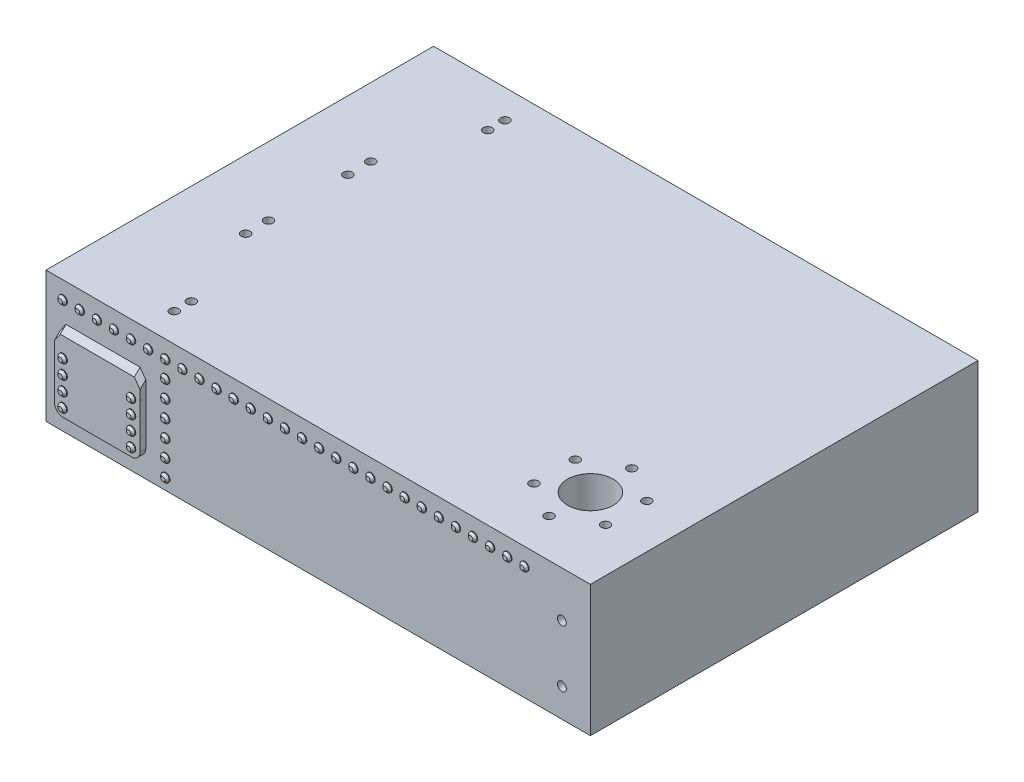
SolidWorks part; units mm, degrees
ref_plane "Front Plane" through (0, 0, 0) normal (0, 0, 1) x (1, 0, 0)
ref_plane "Top Plane" through (0, 0, 0) normal (0, 1, 0) x (1, 0, 0)
ref_plane "Right Plane" through (0, 0, 0) normal (1, 0, 0) x (0, 0, -1)
sketch "Sketch1" plane through (0, 0, 0) normal (0, 1, 0) x (1, 0, 0)
  line L1 (0, 0) -> (191, 0)
  line L2 (0, 0) -> (0, 136)
  line L3 (0, 136) -> (191, 136)
  line L4 (191, 0) -> (191, 136)
  dimension "D1" = 191
  dimension "D2" = 136
extrude "Boss-Extrude1" add sketch "Sketch1" along normal blind 46
sketch "Sketch3" plane through (0, 0, 0) normal (0, -1, 0) x (1, 0, 0)
  line L0 (0, -136) -> (0, 0) construction
  line L1 (5, -5) -> (186, -5)
  line L2 (5, -5) -> (5, -131)
  line L3 (5, -131) -> (186, -131)
  line L4 (186, -5) -> (186, -131)
  line L6 (191, -136) -> (0, -136) construction
  line L7 (191, 0) -> (191, -136) construction
  line L8 (0, 0) -> (191, 0) construction
  dimension "D1" = 5
  dimension "D2" = 5
  dimension "D3" = 5
  dimension "D4" = 5
extrude "Cut-Extrude1" cut sketch "Sketch3" against normal offset from surface (41 mm away) 5 contours L2 L3 L4 L1 up to face at (95.5, 46, -68)
ref_point "FrontLeft"
sketch "Sketch5" plane through (0, 0, -136) normal (0, 0, -1) x (-1, 0, 0)
  line L0 (-191, 46) -> (-119.5, 46)
  line L1 (-191, 46) -> (0, 46) construction
  line L2 (-119.5, 46) -> (-119.5, 0) construction
  line L3 (-191, 0) -> (0, 0) construction
  point P5 (-119.5, 23)
  dimension "D1" = 71.5
sketch "Sketch8" plane through (0, 0, 0) normal (0, 0, 1) x (1, 0, 0)
  line L1 (119.5, 46) -> (119.5, 0) construction
  line L2 (0, 46) -> (191, 46) construction
  line L3 (0, 0) -> (191, 0) construction
  point P0 (119.5, 23)
ref_point "SuspensionMountLeft"
ref_point "SuspensionMountRight"
sketch "Sketch9" plane through (0, 0, -136) normal (0, 0, -1) x (-1, 0, 0)
  line L0 (0, 46) -> (0, 0) construction
  line L1 (-5, 31) -> (-35, 31)
  line L2 (-5, 31) -> (-5, 6.2153)
  line L3 (-5, 6.2153) -> (-35, 6.2153)
  line L4 (-35, 31) -> (-35, 6.2153)
  line L5 (-191, 46) -> (0, 46) construction
  dimension "D1" = 5
  dimension "D2" = 15
  dimension "D3" = 30
extrude "Boss-Extrude2" add sketch "Sketch9" along normal blind 2
chamfer "Chamfer2" distance 2 angle 45 1 edges at (20, 31, -136)
fillet "Fillet1" radius 3 2 edges at (35, 6.2153, -137) (5, 6.2153, -137)
chamfer "Chamfer3" distance 2 angle 45 2 edges at (35, 32, -137) (5, 32, -137)
sketch "Sketch10" plane through (0, 0, 0) normal (0, 0, 1) x (1, 0, 0)
  line L4 (35, 31) -> (5, 31)
  line L5 (35, 6.2153) -> (35, 31)
  line L6 (5, 6.2153) -> (35, 6.2153)
  line L7 (5, 31) -> (5, 6.2153)
  line L8 (35, 31) -> (5, 31)
  line L9 (35, 6.2153) -> (35, 31)
  line L10 (5, 6.2153) -> (35, 6.2153)
  line L11 (5, 31) -> (5, 6.2153)
  dimension "D1" = 0
extrude "Boss-Extrude3" add sketch "Sketch10" along normal blind 2
chamfer "Chamfer4" distance 2 angle 45 1 edges at (20, 31, 0)
fillet "Fillet2" radius 3 2 edges at (35, 6.2153, 1) (5, 6.2153, 1)
chamfer "Chamfer5" distance 2 angle 45 2 edges at (35, 32, 1) (5, 32, 1)
sketch "Sketch23" plane through (0, 0, 2) normal (0, 0, 1) x (1, 0, 0)
  line L0 (8, 9.2153) -> (8, 31) construction
  line L1 (33, 31) -> (7, 31) construction
  line L2 (32, 9.2153) -> (32, 31) construction
  circle A0 centre (8, 9.2153) radius 1.5
  circle A1 centre (32, 9.2153) radius 1.5
  circle A2 centre (8, 14.2153) radius 1.5
  circle A3 centre (32, 14.2153) radius 1.5
  circle A4 centre (8, 19.2153) radius 1.5
  circle A5 centre (32, 19.2153) radius 1.5
  circle A6 centre (8, 24.2153) radius 1.5
  circle A7 centre (32, 24.2153) radius 1.5
  dimension "D1" = 3
  dimension "D2" = 3
  dimension "D3" = 4
extrude "Boss-Extrude8" add sketch "Sketch23" along normal blind 1 contours A4 | A2 | A0 | A1 | A3 | A5 | A7 | A6 region at (8, 9.2153, 2) region at (32, 9.2153, 2) region at (8, 14.2153, 2) region at (32, 14.2153, 2) region at (8, 19.2153, 2) region at (32, 19.2153, 2) region at (32, 24.2153, 2)
chamfer "Chamfer11" distance 0.75 angle 45 8 edges at (9.5, 24.2153, 3) (33.5, 9.2153, 3) (33.5, 14.2153, 3) (33.5, 19.2153, 3) (33.5, 24.2153, 3) (9.5, 9.2153, 3) (9.5, 14.2153, 3) (9.5, 19.2153, 3)
ref_plane "Plane1" through (0, 0, -68) normal (0, 0, 1) x (1, 0, 0)
mirror "Mirror1" about plane through (0, 0, -68) normal (0, 0, 1) of "Chamfer11", "Boss-Extrude8"
sketch "Sketch18" plane through (0, 41, 0) normal (0, -1, 0) x (1, 0, 0)
  line L1 (112.6585, -114) -> (114.6793, -117.5)
  line L2 (114.6793, -117.5) -> (118.7207, -117.5)
  line L3 (118.7207, -117.5) -> (120.7415, -114)
  line L4 (120.7415, -114) -> (118.7207, -110.5)
  line L5 (118.7207, -110.5) -> (114.6793, -110.5)
  line L6 (114.6793, -110.5) -> (112.6585, -114)
  line L7 (112.6585, -66) -> (114.6793, -69.5)
  line L8 (114.6793, -69.5) -> (118.7207, -69.5)
  line L9 (118.7207, -69.5) -> (120.7415, -66)
  line L10 (120.7415, -66) -> (118.7207, -62.5)
  line L11 (118.7207, -62.5) -> (114.6793, -62.5)
  line L12 (114.6793, -62.5) -> (112.6585, -66)
  line L13 (12.4585, -67) -> (14.4793, -70.5)
  line L14 (14.4793, -70.5) -> (18.5207, -70.5)
  line L15 (18.5207, -70.5) -> (20.5415, -67)
  line L16 (20.5415, -67) -> (18.5207, -63.5)
  line L17 (18.5207, -63.5) -> (14.4793, -63.5)
  line L18 (14.4793, -63.5) -> (12.4585, -67)
  line L19 (12.4585, -119.5) -> (14.4793, -123)
  line L20 (14.4793, -123) -> (18.5207, -123)
  line L21 (18.5207, -123) -> (20.5415, -119.5)
  line L22 (20.5415, -119.5) -> (18.5207, -116)
  line L23 (18.5207, -116) -> (14.4793, -116)
  line L24 (14.4793, -116) -> (12.4585, -119.5)
  circle A0 centre (116.7, -114) radius 3.5 construction
  circle A9 centre (116.7, -66) radius 3.5 construction
  circle A10 centre (16.5, -67) radius 3.5 construction
  circle A11 centre (16.5, -119.5) radius 3.5 construction
  point P41 (116.7, -114)
  point P42 (116.7, -66)
  point P43 (16.5, -67)
  point P44 (16.5, -119.5)
extrude "Boss-Extrude7" add sketch "Sketch18" along normal blind 14
sketch "Sketch19" plane through (0, 27, 0) normal (0, -1, 0) x (1, 0, 0)
  line L6 (112.6585, -66) -> (114.6793, -69.5)
  line L7 (114.6793, -69.5) -> (118.7207, -69.5)
  line L8 (118.7207, -69.5) -> (120.7415, -66)
  line L9 (120.7415, -66) -> (118.7207, -62.5)
  line L10 (118.7207, -62.5) -> (114.6793, -62.5)
  line L11 (114.6793, -62.5) -> (112.6585, -66)
  line L12 (112.6585, -66) -> (114.6793, -69.5)
  line L13 (114.6793, -69.5) -> (118.7207, -69.5)
  line L14 (118.7207, -69.5) -> (120.7415, -66)
  line L15 (120.7415, -66) -> (118.7207, -62.5)
  line L16 (118.7207, -62.5) -> (114.6793, -62.5)
  line L17 (114.6793, -62.5) -> (112.6585, -66)
  line L18 (120.7415, -114) -> (118.7207, -110.5)
  line L19 (118.7207, -110.5) -> (114.6793, -110.5)
  line L20 (114.6793, -110.5) -> (112.6585, -114)
  line L21 (112.6585, -114) -> (114.6793, -117.5)
  line L22 (114.6793, -117.5) -> (118.7207, -117.5)
  line L23 (118.7207, -117.5) -> (120.7415, -114)
  line L24 (120.7415, -114) -> (118.7207, -110.5)
  line L25 (118.7207, -110.5) -> (114.6793, -110.5)
  line L26 (114.6793, -110.5) -> (112.6585, -114)
  line L27 (112.6585, -114) -> (114.6793, -117.5)
  line L28 (114.6793, -117.5) -> (118.7207, -117.5)
  line L29 (118.7207, -117.5) -> (120.7415, -114)
  line L30 (12.4585, -119.5) -> (14.4793, -123)
  line L31 (14.4793, -123) -> (18.5207, -123)
  line L32 (18.5207, -123) -> (20.5415, -119.5)
  line L33 (20.5415, -119.5) -> (18.5207, -116)
  line L34 (18.5207, -116) -> (14.4793, -116)
  line L35 (14.4793, -116) -> (12.4585, -119.5)
  line L36 (12.4585, -119.5) -> (14.4793, -123)
  line L37 (14.4793, -123) -> (18.5207, -123)
  line L38 (18.5207, -123) -> (20.5415, -119.5)
  line L39 (20.5415, -119.5) -> (18.5207, -116)
  line L40 (18.5207, -116) -> (14.4793, -116)
  line L41 (14.4793, -116) -> (12.4585, -119.5)
  line L42 (18.5207, -63.5) -> (14.4793, -63.5)
  line L43 (20.5415, -67) -> (18.5207, -63.5)
  line L44 (18.5207, -70.5) -> (20.5415, -67)
  line L45 (14.4793, -70.5) -> (18.5207, -70.5)
  line L46 (12.4585, -67) -> (14.4793, -70.5)
  line L47 (14.4793, -63.5) -> (12.4585, -67)
  line L48 (18.5207, -63.5) -> (14.4793, -63.5)
  line L49 (20.5415, -67) -> (18.5207, -63.5)
  line L50 (18.5207, -70.5) -> (20.5415, -67)
  line L51 (14.4793, -70.5) -> (18.5207, -70.5)
  line L52 (12.4585, -67) -> (14.4793, -70.5)
  line L53 (14.4793, -63.5) -> (12.4585, -67)
  circle A0 centre (116.7, -66) radius 4.0415
  circle A1 centre (16.5, -67) radius 4.0415
  circle A2 centre (16.5, -119.5) radius 4.0415
  circle A3 centre (116.7, -114) radius 4.0415
  dimension "D1" = 0
  dimension "D2" = 0
  dimension "D3" = 0
  dimension "D4" = 0
hole_wizard "CSK for M2 Flat Head Machine Screw1" positions "Sketch21" profile "Sketch20" countersink size "M2" standard "ANSI Metric"
sketch "Sketch21" plane through (0, 27, 0) normal (0, -1, 0) x (-1, 0, 0)
  point P0 (-116.7, 114)
  point P3 (-116.7, 66)
  point P6 (-16.5, 67)
  point P9 (-16.5, 119.5)
sketch "Sketch20" plane through (116.7, 27, -114) normal (1, 0, 0) x (0, 0, -1)
  line L0 (0, 0) -> (0, 13.6009)
  line L1 (0, 13.6009) -> (1, 13)
  line L2 (1, 13) -> (1, 0.4195)
  line L3 (1, 0.4195) -> (1.5, 0)
  line L5 (1.5, 0) -> (0, 0)
  line L6 (-1, 0.4195) -> (-1.5, 0) construction
  line L10 (0, 13.6009) -> (-1, 13) construction
  line L11 (0, -6.35) -> (0, 107.95) construction
  dimension "Hole Dia." = 2
  dimension "Hole Depth" = 13
  dimension "Near C'Sink Dia." = 3
  dimension "Near C'Sink Angle" = 100
  dimension "Drill Angle" = 118
sketch "Sketch22" plane through (0, 0, 0) normal (-1, 0, 0) x (0, 0, 1)
  line L0 (0, 46) -> (0, 0) construction
  line L1 (-10, 10) -> (-80, 10)
  line L2 (-10, 10) -> (-10, 38)
  line L3 (-10, 38) -> (-80, 38)
  line L4 (-80, 10) -> (-80, 38)
  line L5 (-136, 0) -> (0, 0) construction
  line L6 (-136, 46) -> (0, 46) construction
  dimension "D1" = 10
  dimension "D2" = 10
  dimension "D3" = 8
  dimension "D4" = 70
extrude "Cut-Extrude2" [suppressed] cut sketch "Sketch22" against normal up to next
chamfer "Chamfer10" [suppressed] distance 28 angle 45
fillet "Fillet3" [suppressed] radius 3
sketch "Sketch24" plane through (0, 0, 0) normal (0, 0, 1) x (1, 0, 0)
  line L0 (0, 40) -> (191, 40) construction
  line L1 (0, 46) -> (0, 0) construction
  line L2 (191, 46) -> (191, 0) construction
  line L3 (0, 46) -> (191, 46) construction
  circle A0 centre (6, 40) radius 1.5
  circle A1 centre (12, 40) radius 1.5
  circle A2 centre (18, 40) radius 1.5
  circle A3 centre (24, 40) radius 1.5
  circle A4 centre (30, 40) radius 1.5
  circle A5 centre (36, 40) radius 1.5
  circle A6 centre (42, 40) radius 1.5
  circle A7 centre (48, 40) radius 1.5
  circle A8 centre (54, 40) radius 1.5
  circle A9 centre (60, 40) radius 1.5
  circle A10 centre (66, 40) radius 1.5
  circle A11 centre (72, 40) radius 1.5
  circle A12 centre (78, 40) radius 1.5
  circle A13 centre (84, 40) radius 1.5
  circle A14 centre (90, 40) radius 1.5
  circle A15 centre (96, 40) radius 1.5
  circle A16 centre (102, 40) radius 1.5
  circle A17 centre (108, 40) radius 1.5
  circle A18 centre (114, 40) radius 1.5
  circle A19 centre (120, 40) radius 1.5
  circle A20 centre (126, 40) radius 1.5
  circle A21 centre (132, 40) radius 1.5
  circle A22 centre (138, 40) radius 1.5
  circle A23 centre (144, 40) radius 1.5
  circle A24 centre (150, 40) radius 1.5
  circle A25 centre (156, 40) radius 1.5
  circle A26 centre (162, 40) radius 1.5
  circle A27 centre (168, 40) radius 1.5
  circle A28 centre (42, 34) radius 1.5
  circle A29 centre (42, 28) radius 1.5
  circle A30 centre (42, 22) radius 1.5
  circle A31 centre (42, 16) radius 1.5
  circle A32 centre (42, 10) radius 1.5
  circle A33 centre (42, 4) radius 1.5
  dimension "D2" = 3
  dimension "D1" = 6
  dimension "D3" = 6
  dimension "D4" = 28
  dimension "D5" = 7
extrude "Boss-Extrude9" add sketch "Sketch24" along normal blind 1
chamfer "Chamfer12" distance 0.75 angle 45 34 edges at (169.5, 40, 1) (163.5, 40, 1) (157.5, 40, 1) (151.5, 40, 1) (145.5, 40, 1) (139.5, 40, 1) (133.5, 40, 1) (127.5, 40, 1) (121.5, 40, 1) (115.5, 40, 1) (109.5, 40, 1) (103.5, 40, 1) (97.5, 40, 1) (91.5, 40, 1) (85.5, 40, 1) (79.5, 40, 1) (73.5, 40, 1) (67.5, 40, 1) (43.5, 4, 1) (43.5, 10, 1) (43.5, 16, 1) (43.5, 22, 1) (43.5, 28, 1) (43.5, 34, 1) (61.5, 40, 1) (55.5, 40, 1) (49.5, 40, 1) (43.5, 40, 1) (37.5, 40, 1) (31.5, 40, 1) (25.5, 40, 1) (19.5, 40, 1) (13.5, 40, 1) (7.5, 40, 1)
mirror "Mirror3" about plane through (0, 0, -68) normal (0, 0, 1) of "Chamfer12", "Boss-Extrude9"
sketch "Sketch25" plane through (0, 0, -131) normal (0, 0, 1) x (1, 0, 0)
  circle A0 centre (181, 30) radius 1.55 construction
  circle A1 centre (181, 10) radius 1.55 construction
  circle A2 centre (181, 30) radius 1.55
  circle A3 centre (181, 10) radius 1.55
extrude "Cut-Extrude3" cut sketch "Sketch25" against normal through all
sketch "Sketch26" plane through (0, 0, -5) normal (0, 0, -1) x (-1, 0, 0)
  circle A1 centre (-181, 10) radius 1.55
  circle A2 centre (-181, 10) radius 1.55
  circle A3 centre (-181, 30) radius 1.55
  circle A4 centre (-181, 30) radius 1.55
  dimension "D1" = 0
  dimension "D2" = 0
extrude "Cut-Extrude4" cut sketch "Sketch26" against normal through all
sketch "Sketch27" plane through (0, 46, 0) normal (0, 1, 0) x (1, 0, 0)
  line L0 (191, 0) -> (191, 136) construction
  line L1 (0, 0) -> (191, 0) construction
  circle A0 centre (163, 28) radius 1
  dimension "D1" = 2
  dimension "D2" = 28
  dimension "D3" = 28
sketch "Sketch28" plane through (0, 41, 0) normal (0, -1, 0) x (1, 0, 0)
  circle A0 centre (163, -13.5) radius 1.55 construction
  circle A1 centre (163, -28) radius 18
  circle A2 centre (163, -28) radius 18
  circle A3 centre (163, -28) radius 8
  circle A4 centre (163, -28) radius 8
  circle A5 centre (175.5574, -20.75) radius 1.55 construction
  circle A6 centre (175.5574, -35.25) radius 1.55 construction
  circle A7 centre (163, -42.5) radius 1.55 construction
  circle A8 centre (150.4426, -35.25) radius 1.55 construction
  circle A9 centre (150.4426, -20.75) radius 1.55 construction
  circle A10 centre (163, -13.5) radius 1.55
  circle A11 centre (175.5574, -20.75) radius 1.55
  circle A12 centre (175.5574, -35.25) radius 1.55
  circle A13 centre (163, -42.5) radius 1.55
  circle A14 centre (150.4426, -35.25) radius 1.55
  circle A15 centre (150.4426, -20.75) radius 1.55
  circle A17 centre (163, -28) radius 11
  circle A18 centre (163, -28) radius 11
  dimension "D1" = 0
  dimension "D2" = 0
  dimension "D3" = 0
extrude "Cut-Extrude5" cut sketch "Sketch28" against normal through all contours A13 | A12 | A11 | A10 | A15 | A14 region at (163, 41, -13.5) region at (175.5574, 41, -20.75) region at (175.5574, 41, -35.25) region at (163, 41, -42.5) region at (150.4426, 41, -35.25) region at (150.4426, 41, -20.75)
extrude "Cut-Extrude6" cut sketch "Sketch28<3>" against normal through all contours A4 region at (163, 41, -28)
sketch "Sketch28<3>" plane through (0, 41, 0) normal (0, -1, 0) x (1, 0, 0) same geometry as "Sketch28"
extrude "Boss-Extrude10" add sketch "Sketch28<4>" along normal blind 40 contours A18 A4 region at (152.3111, 41, -28)
sketch "Sketch28<4>" plane through (0, 41, 0) normal (0, -1, 0) x (1, 0, 0) same geometry as "Sketch28"
sketch "Sketch29" plane through (0, 1, 0) normal (0, -1, 0) x (1, 0, 0)
  line L0 (163, -28) -> (163, -43.0058) construction
  line L1 (163, -43.0058) -> (162, -43.0058)
  line L2 (163, -43.0058) -> (164, -43.0058)
  line L3 (164, -43.0058) -> (164, -13.0058)
  line L4 (164, -13.0058) -> (162, -13.0058)
  line L5 (162, -13.0058) -> (162, -43.0058)
  dimension "D2" = 1
  dimension "D1" = 1
  dimension "D3" = 30
extrude "Cut-Extrude7" cut sketch "Sketch29" against normal blind 20
ref_plane "Plane2" through (163, 46, -28) normal (0, 0, 1) x (1, 0, 0)
sketch "Sketch30" plane through (163, 46, -28) normal (0, 0, 1) x (1, 0, 0)
  line L0 (11, -5) -> (11, -46) construction
  line L1 (11, -45) -> (11, -5) construction
  line L2 (18, -5) -> (18, -46) construction
  line L3 (18, -5) -> (11, -25.5) construction
  line L4 (23, -5) -> (-158, -5)
  line L5 (-158, -5) -> (-158, -46)
  line L6 (-158, -46) -> (23, -46)
  line L7 (23, -46) -> (23, -5)
  line L8 (23, -5) -> (-158, -5)
  line L9 (-158, -5) -> (-158, -46)
  line L10 (-158, -46) -> (23, -46)
  line L11 (23, -46) -> (23, -5)
  line L12 (17, -7.9286) -> (12, -22.5714)
  line L13 (17, -7.9286) -> (17, -5)
  line L14 (17, -5) -> (17, -4.9)
  line L15 (12, -22.5714) -> (11, -22.5714)
  line L16 (11, -22.5714) -> (10.9, -22.5714)
  line L17 (10.9, -22.5714) -> (10.9, -4.9)
  line L18 (10.9, -4.9) -> (17, -4.9)
  dimension "D2" = 1
  dimension "D3" = 1
  dimension "D4" = 0.1
  dimension "D5" = 0.1
  dimension "D1" = 0
extrude "Boss-Extrude11" add sketch "Sketch30" along normal mid plane 3 contours L17 L16 L15 L12 L13 L8 region at (176.2325, 34.2396, -28)
ref_axis "Axis1" through (163, 46, -28) along (0, -1, 0)
pattern_circular "CirPattern1" count 6 over 360 about axis through (163, 46, -28) along (0, -1, 0) of "Boss-Extrude11"
chamfer "Chamfer13" distance 0.5 angle 45 2 edges at (174, 1, -28) (152, 1, -28)
sketch "Sketch31" plane through (0, 41, 0) normal (0, -1, 0) x (1, 0, 0)
  circle A0 centre (35, -16) radius 1.55 construction
  circle A1 centre (35, -10) radius 1.55 construction
  circle A2 centre (35, -126) radius 1.55 construction
  circle A3 centre (35, -120) radius 1.55 construction
  circle A4 centre (35, -16) radius 1.55
  circle A5 centre (35, -10) radius 1.55
  circle A6 centre (35, -126) radius 1.55
  circle A7 centre (35, -120) radius 1.55
extrude "Cut-Extrude8" cut sketch "Sketch31" against normal up to next
sketch "Sketch32" plane through (5, 0, 0) normal (1, 0, 0) x (0, 0, -1)
  circle A0 centre (125.5, 17.25) radius 1.55 construction
  circle A1 centre (10.5, 17.25) radius 1.55 construction
  circle A2 centre (125.5, 17.25) radius 1.55
  circle A3 centre (10.5, 17.25) radius 1.55
extrude "Cut-Extrude9" cut sketch "Sketch32" against normal up to next
sketch "Sketch34" plane through (5, 0, 0) normal (1, 0, 0) x (0, 0, -1)
  circle A0 centre (46.0692, 8) radius 1.55 construction
  circle A1 centre (89.9308, 8) radius 1.55 construction
  circle A2 centre (46.0692, 8) radius 1.55
  circle A3 centre (89.9308, 8) radius 1.55
extrude "Cut-Extrude10" cut sketch "Sketch34" against normal up to next
sketch "Sketch35" plane through (0, 41, 0) normal (0, -1, 0) x (1, 0, 0)
  circle A0 centre (24, -46.0692) radius 1.55 construction
  circle A1 centre (24, -54.0692) radius 1.55 construction
  circle A2 centre (24, -81.9308) radius 1.55 construction
  circle A3 centre (24, -89.9308) radius 1.55 construction
  circle A4 centre (24, -46.0692) radius 1.55
  circle A5 centre (24, -54.0692) radius 1.55
  circle A6 centre (24, -81.9308) radius 1.55
  circle A7 centre (24, -89.9308) radius 1.55
extrude "Cut-Extrude11" cut sketch "Sketch35" against normal up to next
